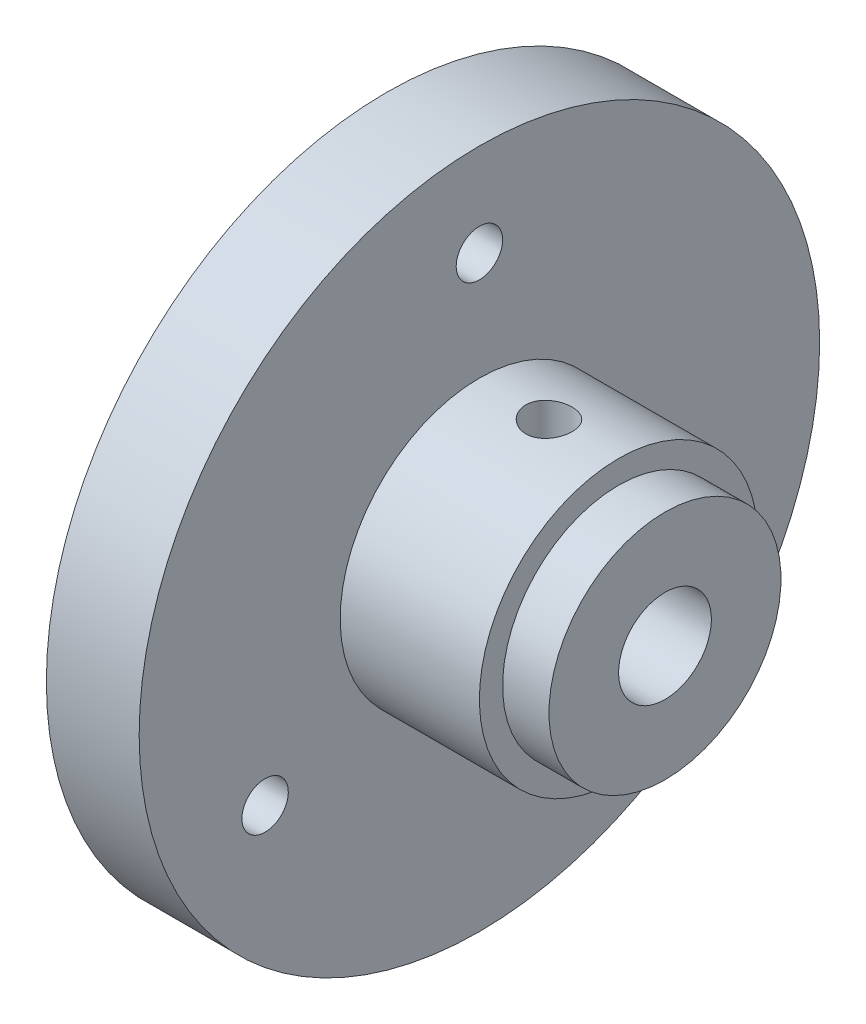
SolidWorks part; units mm, degrees
ref_plane "Plan de face" through (0, 0, 0) normal (0, 0, 1) x (1, 0, 0)
ref_plane "Plan de dessus" through (0, 0, 0) normal (0, 1, 0) x (1, 0, 0)
ref_plane "Plan de droite" through (0, 0, 0) normal (1, 0, 0) x (0, 0, -1)
sketch "Esquisse1" plane through (0, 0, 0) normal (0, 0, 1) x (1, 0, 0)
  line L0 (0, 0) -> (-18, 0) construction
  line L1 (0, 3) -> (-18, 3)
  line L3 (-3, 9) -> (-12, 9)
  line L7 (-12, 22) -> (-18, 22)
  line L8 (-18, 3) -> (-18, 22)
  line L9 (-18, 3) -> (-18, 0) construction
  line L10 (-3, 9) -> (-3, 7.5)
  line L11 (-12, 22) -> (-12, 9)
  line L14 (-3, 7.5) -> (0, 7.5)
  line L15 (0, 3) -> (0, 7.5)
  line L16 (0, 3) -> (0, 0) construction
  point P0 (0, -0.0338)
  dimension "D1" = 3
  dimension "D2" = 22
  dimension "D3" = 6
  dimension "D4" = 6
  dimension "D5" = 9
  dimension "D6" = 7.5
  dimension "D7" = 3
revolve "Révolution1" add sketch "Esquisse1" angle 360 about L0
sketch "Esquisse2" plane through (-12, 0, 0) normal (1, 0, 0) x (0, 0, -1)
  line L0 (0, 16) -> (0, 0) construction
  circle A0 centre (0, 16) radius 1.5
  circle A1 centre (13.8564, -8) radius 1.5
  circle A2 centre (-13.8564, -8) radius 1.5
  point P2 (19.2142, -4.521)
  point P5 (0, 0)
  point P11 (0, 0)
  dimension "D1" = 3
  dimension "D2" = 16
  dimension "D3" = 3
extrude "Enlèv. mat.-Extru.1" cut sketch "Esquisse2" against normal through all
ref_plane "Plan2" through (0, 9, 0) normal (0, 1, 0) x (1, 0, 0)
sketch "Esquisse3" plane through (0, 9, 0) normal (0, 1, 0) x (1, 0, 0)
  line L0 (-3, 0) -> (-12, 0) construction
  line L1 (-12, -1.5) -> (-12, 1.5) construction
  line L2 (-3, -7.5) -> (-3, 7.5) construction
  circle A0 centre (-7.5, 0) radius 1.5
  point P8 (-7.5, 0)
  point P9 (-3, 0)
  dimension "D1" = 3
extrude "Enlèv. mat.-Extru.2" cut sketch "Esquisse3" against normal up to next
